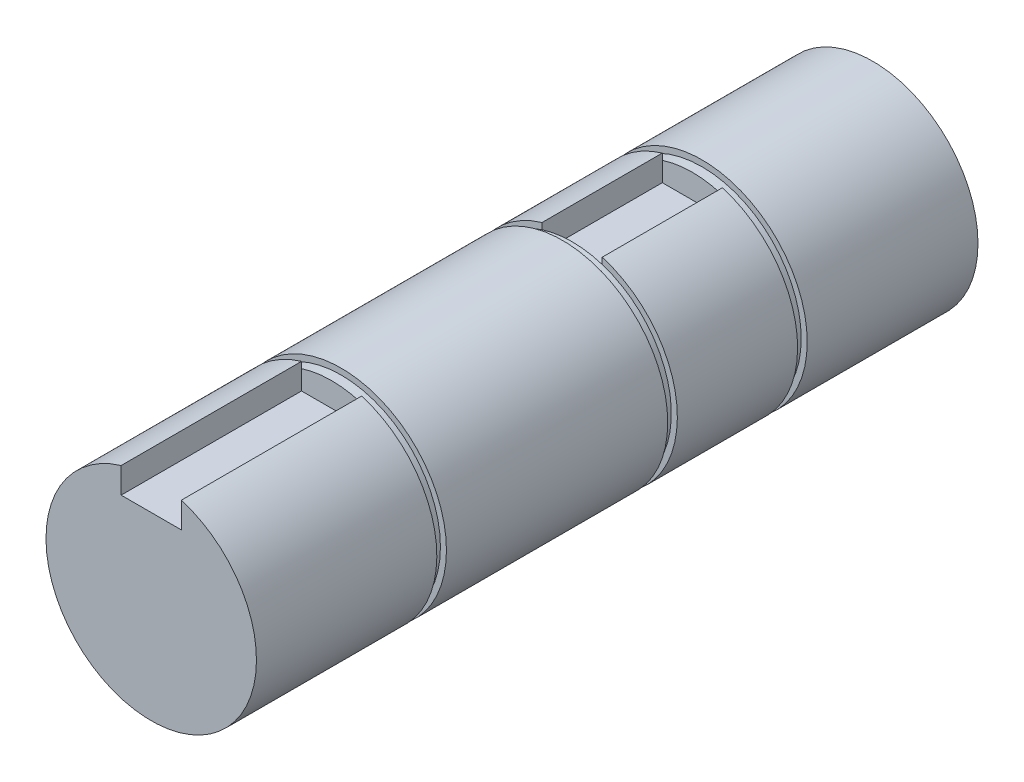
SolidWorks part; units mm, degrees
ref_plane "Front Plane" through (0, 0, 0) normal (0, 0, 1) x (1, 0, 0)
ref_plane "Top Plane" through (0, 0, 0) normal (0, 1, 0) x (1, 0, 0)
ref_plane "Right Plane" through (0, 0, 0) normal (1, 0, 0) x (0, 0, -1)
sketch "Sketch1" plane through (0, 0, 0) normal (0, 0, 1) x (1, 0, 0)
  circle A0 centre (0, 0) radius 17.5
  dimension "D1" = 35
extrude "Boss-Extrude1" add sketch "Sketch1" along normal blind 120
sketch "Sketch2" plane through (0, 0, 0) normal (0, 0, 1) x (1, 0, 0)
  line L0 (-5, 16.7705) -> (-5, 12.5)
  line L1 (-5, 12.5) -> (5, 12.5)
  line L2 (5, 12.5) -> (5, 16.7705)
  circle A0 centre (0, 0) radius 17.5 construction
  arc A1 (-5, 16.7705) -> (5, 16.7705) centre (0, 0) cw
  dimension "D1" = 5
  dimension "D2" = 10
extrude "Cut-Extrude1" cut sketch "Sketch2" along normal blind 20 from offset 30
extrude "Cut-Extrude2" cut sketch "Sketch2<2>" along normal blind 30 from offset 90
sketch "Sketch2<2>" plane through (0, 0, 0) normal (0, 0, 1) x (1, 0, 0) same geometry as "Sketch2"
sketch "Sketch3" plane through (0, 0, 0) normal (1, 0, 0) x (0, 0, -1)
  line L0 (-30, 17.5) -> (-30, 16.7705) construction
  line L1 (-30, 17.5) -> (-28.4, 17.5)
  line L2 (-30, 17.5) -> (-30, 16.5)
  line L3 (-30, 16.5) -> (-28.4, 16.5)
  line L4 (-28.4, 17.5) -> (-28.4, 16.5)
  line L5 (0, 0) -> (-120, 0) construction
  line L8 (-120, 16.7705) -> (-120, -17.5) construction
  line L9 (-51.6, 17.5) -> (-50, 17.5)
  line L10 (-51.6, 17.5) -> (-51.6, 16.5)
  line L11 (-51.6, 16.5) -> (-50, 16.5)
  line L12 (-50, 17.5) -> (-50, 16.5)
  line L13 (-50, 16.7705) -> (-50, 17.5) construction
  line L14 (-90, 17.5) -> (-88.4, 17.5)
  line L15 (-90, 17.5) -> (-90, 16.5)
  line L16 (-90, 16.5) -> (-88.4, 16.5)
  line L17 (-88.4, 17.5) -> (-88.4, 16.5)
  line L18 (-90, 17.5) -> (-90, 16.7705) construction
  line L19 (-50, 17.5) -> (-90, 17.5) construction
  point P17 (0, 0)
  dimension "D1" = 1
  dimension "D2" = 1.6
  dimension "D3" = 17.5
  dimension "D4" = 1
  dimension "D5" = 1.6
  dimension "D6" = 1
  dimension "D7" = 1.6
revolve "Cut-Revolve2" cut sketch "Sketch3" angle 360 about L5
